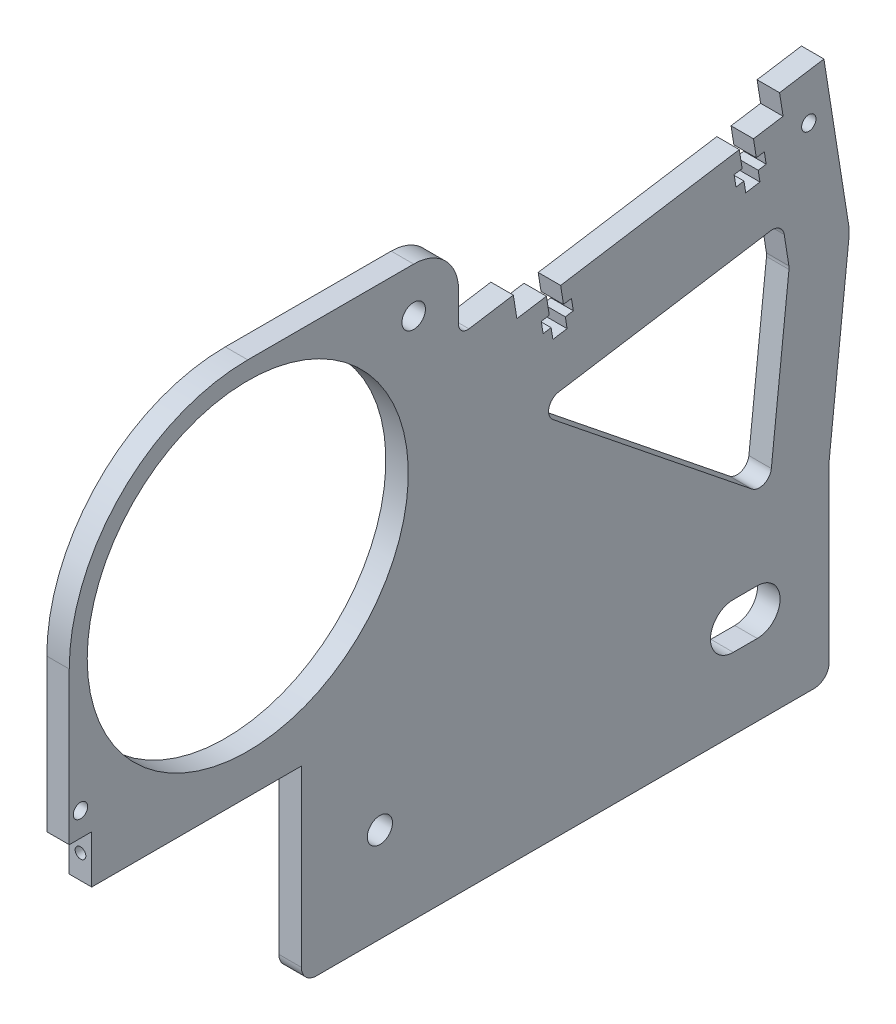
SolidWorks part; units mm, degrees
ref_plane "Front Plane" through (0, 0, 0) normal (0, 0, 1) x (1, 0, 0)
ref_plane "Top Plane" through (0, 0, 0) normal (0, 1, 0) x (1, 0, 0)
ref_plane "Right Plane" through (0, 0, 0) normal (1, 0, 0) x (0, 0, -1)
sketch "Sketch1" plane through (0, 0, 0) normal (1, 0, 0) x (0, 0, -1)
  line L0 (-28.1703, 0) -> (77.3828, 0)
  line L1 (80.5578, 3.175) -> (80.5578, 40.132)
  line L2 (-80.5578, 82.55) -> (-80.5578, 50.292)
  line L3 (24.9961, 92.2761) -> (21.9857, 91.7993) construction
  line L4 (-75.7953, 50.292) -> (-75.7953, 40.132)
  line L5 (65.3178, 20.066) -> (60.2378, 20.066) construction
  line L6 (65.3178, 15.2273) -> (60.2378, 15.2273)
  line L7 (-75.7953, 40.132) -> (-31.3453, 40.132)
  line L8 (24.6236, 94.628) -> (24.9961, 92.2761) construction
  line L9 (21.9857, 91.7993) -> (21.6131, 94.1512) construction
  line L10 (-31.3453, 40.132) -> (-31.3453, 3.175)
  line L11 (-80.5578, 50.292) -> (-75.7953, 50.292)
  line L12 (65.3178, 24.9047) -> (60.2378, 24.9047)
  line L13 (21.6131, 94.1512) -> (19.9198, 93.883) construction
  line L14 (19.9198, 93.883) -> (19.5274, 96.3604) construction
  line L15 (19.5274, 96.3604) -> (21.2208, 96.6286) construction
  line L16 (21.2208, 96.6286) -> (20.6198, 100.423) construction
  line L17 (20.6198, 100.423) -> (14.348, 99.4297) construction
  line L18 (14.348, 99.4297) -> (13.6029, 104.1335) construction
  line L19 (13.6029, 104.1335) -> (4.1952, 102.6435) construction
  line L20 (1.9922, 104.525) -> (1.9922, 110.875) construction
  line L21 (-7.5328, 120.4) -> (-42.7078, 120.4) construction
  line L22 (24.9961, 92.2761) -> (21.9857, 91.7993)
  line L23 (24.6236, 94.628) -> (24.9961, 92.2761)
  line L24 (21.9857, 91.7993) -> (21.6131, 94.1512)
  line L25 (21.6131, 94.1512) -> (19.9198, 93.883)
  line L26 (19.9198, 93.883) -> (19.5274, 96.3604)
  line L27 (19.5274, 96.3604) -> (21.2208, 96.6286)
  line L28 (21.2208, 96.6286) -> (20.6198, 100.423)
  line L29 (20.6198, 100.423) -> (14.348, 99.4297)
  line L30 (14.348, 99.4297) -> (13.6029, 104.1335)
  line L31 (13.6029, 104.1335) -> (4.1952, 102.6435)
  line L32 (1.9922, 104.525) -> (1.9922, 110.875)
  line L33 (-7.5328, 120.4) -> (-42.7078, 120.4)
  line L35 (80.5578, 40.132) -> (84.7717, 79.1961)
  line L36 (25.9246, 97.3736) -> (26.317, 94.8962) construction
  line L37 (26.317, 94.8962) -> (24.6236, 94.628) construction
  line L38 (24.2312, 97.1054) -> (25.9246, 97.3736) construction
  line L39 (23.6303, 100.8998) -> (24.2312, 97.1054) construction
  line L51 (70.0493, 113.0738) -> (70.7944, 108.3699) construction
  line L52 (79.4571, 114.5638) -> (70.0493, 113.0738) construction
  line L55 (68.3027, 44.9396) -> (72.0438, 79.6202) construction
  line L56 (68.1298, 88.6604) -> (23.2189, 81.5472) construction
  line L57 (22.0267, 77.0573) -> (64.1879, 43.2308) construction
  line L58 (84.7184, 81.3449) -> (79.4571, 114.5638) construction
  line L59 (64.5225, 107.3765) -> (65.1235, 103.5821) construction
  line L60 (25.9246, 97.3736) -> (26.317, 94.8962)
  line L61 (26.317, 94.8962) -> (24.6236, 94.628)
  line L62 (24.2312, 97.1054) -> (25.9246, 97.3736)
  line L63 (23.6303, 100.8998) -> (24.2312, 97.1054)
  line L64 (62.113, 103.1053) -> (61.5121, 106.8997) construction
  line L65 (60.4196, 102.8371) -> (62.113, 103.1053) construction
  line L66 (60.812, 100.3597) -> (60.4196, 102.8371) construction
  line L67 (62.5054, 100.6279) -> (60.812, 100.3597) construction
  line L68 (62.8779, 98.276) -> (62.5054, 100.6279) construction
  line L69 (65.8884, 98.7528) -> (62.8779, 98.276) construction
  line L70 (65.5159, 101.1047) -> (65.8884, 98.7528) construction
  line L71 (67.2093, 101.3729) -> (65.5159, 101.1047) construction
  line L72 (66.8169, 103.8503) -> (67.2093, 101.3729) construction
  line L73 (65.1235, 103.5821) -> (66.8169, 103.8503) construction
  line L74 (84.7184, 81.3449) -> (79.4571, 114.5638)
  line L75 (70.0493, 113.0738) -> (70.7944, 108.3699)
  line L76 (79.4571, 114.5638) -> (70.0493, 113.0738)
  line L77 (64.5225, 107.3765) -> (65.1235, 103.5821)
  line L79 (68.3027, 44.9396) -> (72.0438, 79.6202)
  line L80 (68.1298, 88.6604) -> (23.2189, 81.5472)
  line L81 (22.0267, 77.0573) -> (64.1879, 43.2308)
  line L82 (62.113, 103.1053) -> (61.5121, 106.8997)
  line L83 (60.4196, 102.8371) -> (62.113, 103.1053)
  line L84 (60.812, 100.3597) -> (60.4196, 102.8371)
  line L85 (62.5054, 100.6279) -> (60.812, 100.3597)
  line L86 (62.8779, 98.276) -> (62.5054, 100.6279)
  line L87 (65.8884, 98.7528) -> (62.8779, 98.276)
  line L88 (65.5159, 101.1047) -> (65.8884, 98.7528)
  line L89 (67.2093, 101.3729) -> (65.5159, 101.1047)
  line L90 (66.8169, 103.8503) -> (67.2093, 101.3729)
  line L91 (65.1235, 103.5821) -> (66.8169, 103.8503)
  line L92 (70.7944, 108.3699) -> (64.5225, 107.3765) construction
  line L93 (61.5121, 106.8997) -> (23.6303, 100.8998) construction
  line L94 (72.0272, 80.29) -> (71.0359, 86.549) construction
  line L95 (70.7944, 108.3699) -> (64.5225, 107.3765)
  line L96 (61.5121, 106.8997) -> (23.6303, 100.8998)
  line L97 (72.0272, 80.29) -> (71.0359, 86.549)
  arc A0 (65.3178, 15.2273) -> (65.3178, 24.9047) centre (65.3178, 20.066) ccw
  circle A1 centre (-42.7078, 82.55) radius 31.5 construction
  circle A2 centre (65.3178, 20.066) radius 77.47 construction
  circle A3 centre (-78.1765, 55.372) radius 1.524
  arc A4 (60.2378, 24.9047) -> (60.2378, 15.2273) centre (60.2378, 20.066) ccw
  arc A5 (-42.7078, 120.4) -> (-80.5578, 82.55) centre (-42.7078, 82.55) ccw
  arc A6 (-28.1703, 0) -> (-31.3453, 3.175) centre (-28.1703, 3.175) cw
  arc A7 (77.3828, 0) -> (80.5578, 3.175) centre (77.3828, 3.175) ccw
  circle A9 centre (76.2432, 104.411) radius 1.524 construction
  circle A10 centre (76.2432, 104.411) radius 1.524
  circle A11 centre (-14.6922, 20.066) radius 2.667
  arc A12 (1.9922, 104.525) -> (4.1952, 102.6435) centre (3.8972, 104.525) ccw construction
  arc A13 (1.9922, 110.875) -> (-7.5328, 120.4) centre (-7.5328, 110.875) ccw construction
  arc A14 (1.9922, 104.525) -> (4.1952, 102.6435) centre (3.8972, 104.525) ccw
  arc A15 (1.9922, 110.875) -> (-7.5328, 120.4) centre (-7.5328, 110.875) ccw
  circle A16 centre (-42.7078, 82.55) radius 34.04
  arc A18 (84.7717, 79.1961) -> (84.7184, 81.3449) centre (76.6695, 80.0701) ccw construction
  arc A20 (23.2189, 81.5472) -> (22.0267, 77.0573) centre (23.6162, 79.0385) ccw construction
  arc A21 (64.1879, 43.2308) -> (68.3027, 44.9396) centre (65.7774, 45.212) ccw construction
  arc A22 (71.0359, 86.549) -> (68.1298, 88.6604) centre (68.5271, 86.1517) ccw construction
  arc A23 (84.7717, 79.1961) -> (84.7184, 81.3449) centre (76.6695, 80.0701) ccw
  arc A24 (72.0438, 79.6202) -> (72.0272, 80.29) centre (69.5185, 79.8927) ccw construction
  arc A25 (23.2189, 81.5472) -> (22.0267, 77.0573) centre (23.6162, 79.0385) ccw
  arc A26 (64.1879, 43.2308) -> (68.3027, 44.9396) centre (65.7774, 45.212) ccw
  circle A29 centre (-7.5328, 110.875) radius 2.4892 construction
  circle A30 centre (-7.5328, 110.875) radius 2.4892
  arc A31 (71.0359, 86.549) -> (68.1298, 88.6604) centre (68.5271, 86.1517) ccw
  arc A32 (72.0438, 79.6202) -> (72.0272, 80.29) centre (69.5185, 79.8927) ccw
  point P13 (62.7778, 20.066)
  dimension "D4" = 9.6774
  dimension "D7" = 4.7625
  dimension "D8" = 63
  dimension "D12" = 3.175
  dimension "D14" = 2.54
  dimension "D15" = 154.94
  dimension "D18" = 5.334
  dimension "D19" = 5.08
  dimension "D17" = 3.048
  dimension "D2" = 40.132
  dimension "D3" = 20.066
  dimension "D5" = 15.24
  dimension "D6" = 44.45
  dimension "D10" = 161.1156
  dimension "D11" = 95.25
  dimension "D21" = 5.08
  dimension "D22" = 10.16
  dimension "D16" = 2.3813
extrude "Boss-Extrude1" add sketch "Sketch1" along normal blind 4.7625
sketch "Sketch2" plane through (0, 0, 75.7953) normal (0, 0, 1) x (1, 0, 0)
  line L0 (0, 50.292) -> (0, 40.132) construction
  line L1 (4.7625, 40.132) -> (0, 40.132) construction
  circle A0 centre (2.3813, 45.212) radius 1.1303
  point P4 (0, 45.212)
  point P7 (2.3813, 40.132)
  dimension "D1" = 2.2606
extrude "Cut-Extrude1" cut sketch "Sketch2" against normal blind 6.35
sketch "Sketch3" plane through (0, 0, 0) normal (-1, 0, 0) x (0, 0, 1)
  circle A0 centre (-60.2378, 20.066) radius 70 construction
